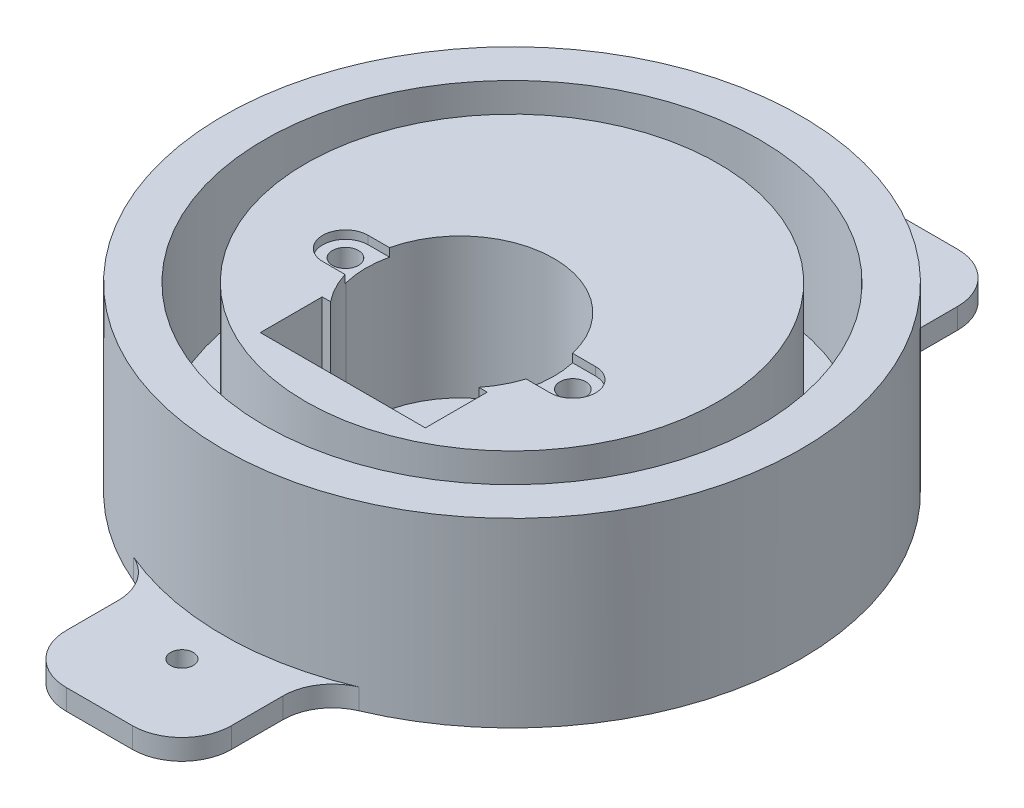
SolidWorks part; units mm, degrees
ref_plane "Front Plane" through (0, 0, 0) normal (0, 0, 1) x (1, 0, 0)
ref_plane "Top Plane" through (0, 0, 0) normal (0, 1, 0) x (1, 0, 0)
ref_plane "Right Plane" through (0, 0, 0) normal (1, 0, 0) x (0, 0, -1)
sketch "Sketch2" plane through (0, 0, 0) normal (0, 1, 0) x (1, 0, 0)
  circle A1 centre (0, 0) radius 4.4958 construction
  circle A2 centre (0, -8.001) radius 14.4145 construction
  circle A4 centre (0, 0) radius 44.45
  circle A5 centre (0, 0) radius 38.1
  dimension "D1" = 8.001
  dimension "D2" = 28.829
  dimension "D3" = 8.9916
  dimension "D4" = 88.9
  dimension "D5" = 76.2
extrude "Boss-Extrude1" add sketch "Sketch2" along normal blind 6.35 contours A5 | A4 A5 region at (-43.1928, 0, 0) region at (0, 0, 0)
extrude "Boss-Extrude2" add sketch "Sketch2<3>" along normal blind 27.94
sketch "Sketch2<3>" plane through (0, 0, 0) normal (0, 1, 0) x (1, 0, 0) same geometry as "Sketch2"
sketch "Sketch3" plane through (0, 6.35, 0) normal (0, 1, 0) x (1, 0, 0)
  line L0 (0, -8.0001) -> (0, -0.0001)
  line L1 (0, -0.0001) -> (-4.5, -0.0001) construction
  line L2 (-14.0193, -4.5001) -> (-17.4719, -4.5001)
  line L3 (-17.4719, -11.5001) -> (-14.0193, -11.5001)
  line L4 (14.0193, -11.5001) -> (17.5281, -11.5001)
  line L5 (17.5281, -4.5001) -> (14.0193, -4.5001)
  circle A0 centre (0, 0) radius 31.75
  arc A1 (14.0193, -4.5001) -> (-14.0193, -4.5001) centre (0, -8.0001) ccw
  arc A2 (-17.4719, -4.5001) -> (-17.4719, -11.5001) centre (-17.4719, -8.0001) ccw
  arc A3 (-14.0193, -11.5001) -> (14.0193, -11.5001) centre (0, -7.4056) ccw
  arc A4 (17.5281, -11.5001) -> (17.5281, -4.5001) centre (17.5281, -8.0001) ccw
  arc A5 (-14.0193, -4.5001) -> (-14.0193, -11.5001) centre (0, -8.0001) ccw
  arc A6 (14.0193, -4.5001) -> (14.0193, -11.5001) centre (0, -8.0001) cw
  point P3 (0, 0)
  point P21 (0, 0)
  point P22 (0, 0)
  point P23 (0, 0)
  point P24 (0, 0)
  point P25 (0, 0)
  point P26 (0, 0)
  point P27 (0, 0)
  point P28 (0, 0)
  dimension "D1" = 63.5
  dimension "D2" = 14.605
extrude "Boss-Extrude4" add sketch "Sketch3" along normal blind 21.59 contours L5 A6 L4 A4 | A5 L2 A2 L3 | A0 A4 L4 A3 L3 A2 L2 A1 L5 region at (-17.3141, 6.35, 8.0001) region at (17.3417, 6.35, 8.0001) region at (-30.852, 6.35, 0)
sketch "Sketch4" plane through (0, 27.94, 0) normal (0, 1, 0) x (1, 0, 0)
  line L0 (0.1313, -8.2627) -> (0.1313, -0.2627)
  line L1 (0.1313, -0.2627) -> (-4.3687, -0.2627) construction
  line L2 (-13.4241, -4.7627) -> (-17.3687, -4.7627)
  line L3 (-17.3687, -11.7627) -> (-13.4241, -11.7627)
  line L4 (13.6868, -11.7627) -> (17.6313, -11.7627)
  line L5 (17.6313, -4.7627) -> (13.6868, -4.7627)
  circle A0 centre (0.1313, -0.2626) radius 31.75 construction
  arc A1 (13.6868, -4.7627) -> (-13.4241, -4.7627) centre (0.1313, -8.2627) ccw
  arc A2 (-17.3687, -4.7627) -> (-17.3687, -11.7627) centre (-17.3687, -8.2627) ccw
  arc A3 (-13.4241, -11.7627) -> (13.6868, -11.7627) centre (0.1313, -8.2627) ccw
  arc A4 (17.6313, -11.7627) -> (17.6313, -4.7627) centre (17.6313, -8.2627) ccw
  circle A5 centre (-17.3687, -8.2627) radius 2
  circle A6 centre (17.6313, -8.2627) radius 2
  arc M8 (-14.0193, -11.5001) -> (14.0193, -11.5001) centre (0, -8.0001) cw
  arc M25 (14.0193, -11.5001) -> (-14.0193, -11.5001) centre (0, -7.4056) cw
  dimension "D1" = 63.5
  dimension "D2" = 4
  dimension "D3" = 35
extrude "Cut-Extrude1" cut sketch "Sketch4" against normal blind 1.27 contours L4 A4 L5 A6 M8 M25 | L2 A2 L3 A5 M25 M8 region at (-14.5475, 27.94, 8.136) region at (15.8568, 27.94, 4.863)
extrude "Cut-Extrude2" cut sketch "Sketch4<3>" against normal blind 8.89 contours A5 | A6 region at (-17.3687, 27.94, 8.2627) region at (17.6313, 27.94, 8.2627)
sketch "Sketch4<3>" plane through (0, 27.94, 0) normal (0, 1, 0) x (1, 0, 0) same geometry as "Sketch4"
sketch "Sketch5" plane through (0, 0, 0) normal (0, -1, 0) x (1, 0, 0)
  line L0 (-12.7, 63.5) -> (-12.7, 38.1)
  line L1 (-12.7, 38.1) -> (12.7, 38.1)
  line L2 (12.7, 38.1) -> (12.7, 63.5)
  line L3 (12.7, 63.5) -> (-12.7, 63.5)
  line L4 (0, 0) -> (0, 38.1) construction
  line L5 (12.7, -63.5) -> (12.7, -38.1)
  line L6 (12.7, -38.1) -> (-12.7, -38.1)
  line L7 (-12.7, -38.1) -> (-12.7, -63.5)
  line L8 (-12.7, -63.5) -> (12.7, -63.5)
  line L9 (0, 0) -> (0, -38.1) construction
  circle A1 centre (0, 0) radius 44.45 construction
  point P16 (0, 0)
  dimension "D1" = 19.05
  dimension "D2" = 25.4
  dimension "D3" = 25.4
  dimension "D4" = 2
extrude "Boss-Extrude6" add sketch "Sketch5" against normal blind 3.175
fillet "Fillet1" radius 7.62 8 edges at (12.7, 1.5875, 63.5) (-12.7, 1.5875, 63.5) (-12.7, 1.5875, 42.5971) (12.7, 1.5875, 42.5971) (-12.7, 1.5875, -63.5) (12.7, 1.5875, -63.5) (12.7, 1.5875, -42.5971) (-12.7, 1.5875, -42.5971)
sketch "Sketch6" plane through (0, 0, 0) normal (0, 0, 1) x (1, 0, 0)
  line L0 (0, 0) -> (0, 14.0293) construction
sketch "Sketch7" plane through (0, 3.175, 0) normal (0, 1, 0) x (1, 0, 0)
  circle A0 centre (0, 50.8) radius 1.75
  circle A1 centre (0, -50.8) radius 1.75
  point P4 (0, 0)
  point P6 (0, 0)
  dimension "D1" = 3.5
  dimension "D2" = 50.8
  dimension "D3" = 50.8
extrude "Cut-Extrude3" cut sketch "Sketch7" against normal blind 11.43
sketch "Sketch8" plane through (0, 27.94, 0) normal (0, 1, 0) x (1, 0, 0)
  line L0 (0, 0) -> (0, -16.51) construction
  line L1 (-12.7, -26.035) -> (12.7, -26.035)
  line L2 (-12.7, -26.035) -> (-12.7, -16.51)
  line L3 (-12.7, -16.51) -> (12.7, -16.51)
  line L4 (12.7, -26.035) -> (12.7, -16.51)
  point P7 (0, 0)
  dimension "D1" = 9.525
  dimension "D2" = 25.4
  dimension "D3" = 16.51
extrude "Cut-Extrude4" cut sketch "Sketch8" against normal up to surface (21.59 mm away) up to face at (0, 6.35, 7.7805)
